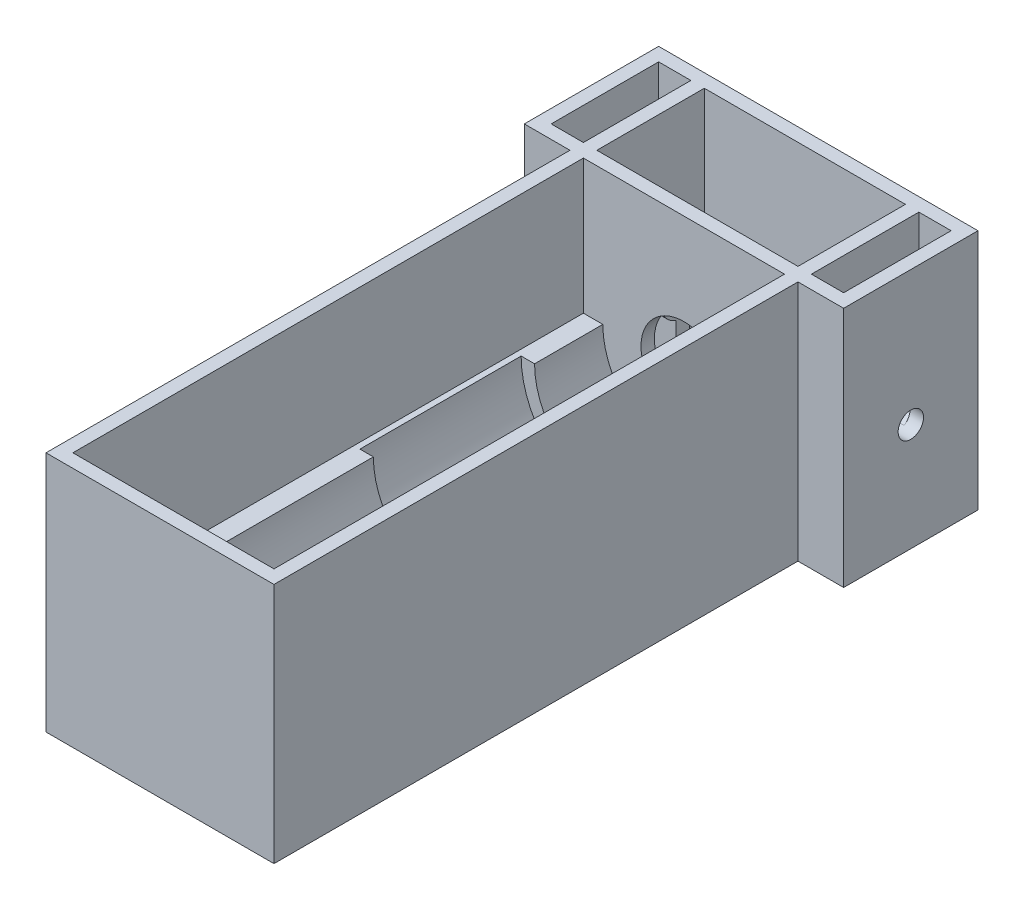
SolidWorks part; units mm, degrees
ref_plane "Front Plane" through (0, 0, 0) normal (0, 0, 1) x (1, 0, 0)
ref_plane "Top Plane" through (0, 0, 0) normal (0, 1, 0) x (1, 0, 0)
ref_plane "Right Plane" through (0, 0, 0) normal (1, 0, 0) x (0, 0, -1)
sketch "Sketch1" plane through (0, 0, 0) normal (0, 0, 1) x (1, 0, 0)
  line L1 (-26.9397, 0) -> (26.9397, 0)
  line L2 (-26.9397, 0) -> (-26.9397, 6.35)
  line L3 (-23.7647, 6.35) -> (23.7647, 6.35)
  line L4 (26.9397, 0) -> (26.9397, 6.35)
  line L6 (-26.9397, 6.35) -> (-26.9397, 57.15)
  line L7 (-26.9397, 57.15) -> (-23.7647, 57.15)
  line L8 (-23.7647, 6.35) -> (-23.7647, 57.15)
  line L10 (26.9397, 6.35) -> (26.9397, 57.15)
  line L11 (26.9397, 57.15) -> (23.7647, 57.15)
  line L12 (23.7647, 6.35) -> (23.7647, 57.15)
  dimension "D1" = 3.175
  dimension "D2" = 53.8795
  dimension "D3" = 6.35
  dimension "D4" = 50.8
extrude "Boss-Extrude1" add sketch "Sketch1" along normal mid plane 25.4
sketch "Sketch2" plane through (0, 0, -12.7) normal (0, 0, -1) x (-1, 0, 0)
  line L0 (26.9397, 0) -> (-26.9397, 0) construction
  line L1 (-26.9397, 57.15) -> (26.9397, 57.15)
  line L2 (-26.9397, 57.15) -> (-26.9397, 0)
  line L3 (-26.9397, 0) -> (26.9397, 0)
  line L4 (26.9397, 57.15) -> (26.9397, 0)
extrude "Boss-Extrude2" add sketch "Sketch2" along normal blind 3.175
sketch "Sketch6" plane through (0, 0, 0) normal (0, 0, 1) x (1, 0, 0)
  line L0 (-23.7647, 25.4) -> (-16.1447, 25.4)
  line L3 (-16.1447, 25.4) -> (-16.1447, 30.48)
  line L4 (-16.1447, 30.48) -> (-21.2247, 30.48)
  line L5 (-21.2247, 30.48) -> (-23.7647, 33.02)
  line L6 (0, 25.4) -> (0, 0) construction
  line L7 (-23.7647, 33.02) -> (-23.7647, 25.4)
  line L9 (-23.7647, 6.35) -> (-23.7647, 57.15) construction
  line L10 (23.7647, 33.02) -> (23.7647, 25.4)
  line L11 (21.2247, 30.48) -> (23.7647, 33.02)
  line L12 (16.1447, 30.48) -> (21.2247, 30.48)
  line L13 (16.1447, 25.4) -> (16.1447, 30.48)
  line L15 (23.7647, 25.4) -> (16.1447, 25.4)
  dimension "D1" = 5.08
  dimension "D2" = 5.08
  dimension "D3" = 7.62
  dimension "D4" = 7.62
  dimension "D5" = 25.4
revolve "Revolve2" add sketch "Sketch6" angle 360 about L0
sketch "Sketch3" plane through (0, 0, 0) normal (1, 0, 0) x (0, 0, -1)
  circle A0 centre (0, 25.4) radius 3
  circle A1 centre (0, 25.4) radius 5.08 construction
  dimension "D2" = 6
extrude "Cut-Extrude2" cut sketch "Sketch3" against normal through all both and the other way through all
sketch "Sketch5" plane through (0, 0, 0) normal (0, -1, 0) x (1, 0, 0)
  line L1 (26.9397, -15.875) -> (-26.9397, -15.875)
  line L2 (26.9397, -15.875) -> (26.9397, -41.275)
  line L3 (26.9397, -41.275) -> (-26.9397, -41.275)
  line L4 (-26.9397, -15.875) -> (-26.9397, -41.275)
  circle A0 centre (7.8897, -28.575) radius 3.4925
  circle A1 centre (-17.5103, -28.575) radius 3.4925
  point P9 (26.9397, -28.575)
  dimension "D2" = 6.985
  dimension "D1" = 25.4
  dimension "D3" = 19.05
  dimension "D4" = 2
extrude "Boss-Extrude3" add sketch "Sketch5" against normal blind 6.35
sketch "Sketch7" plane through (0, 0, 0) normal (0, 0, 1) x (1, 0, 0)
  line L0 (23.7647, 6.35) -> (-23.7647, 6.35) construction
  line L1 (-23.7647, 21.9594) -> (-16.1447, 21.9594)
  line L2 (-23.7647, 21.9594) -> (-23.7647, 6.35)
  line L3 (-23.7647, 6.35) -> (-16.1447, 6.35)
  line L4 (-16.1447, 21.9594) -> (-16.1447, 6.35)
  line L5 (-23.7647, 21.9594) -> (-16.1447, 6.35) construction
  line L6 (-23.7647, 6.35) -> (-16.1447, 21.9594) construction
  line L8 (0, 0) -> (0, 25.6446) construction
  line L9 (-26.9397, 0) -> (26.9397, 0) construction
  line L10 (23.7647, 6.35) -> (16.1447, 21.9594) construction
  line L11 (23.7647, 21.9594) -> (16.1447, 6.35) construction
  line L12 (16.1447, 21.9594) -> (16.1447, 6.35)
  line L13 (23.7647, 6.35) -> (16.1447, 6.35)
  line L14 (23.7647, 21.9594) -> (23.7647, 6.35)
  line L15 (23.7647, 21.9594) -> (16.1447, 21.9594)
  line L16 (-23.7647, 6.35) -> (-23.7647, 57.15) construction
  line L17 (-16.1447, 20.32) -> (-16.1447, 30.48) construction
  point P4 (-19.9547, 14.1547)
  point P18 (19.9547, 14.1547)
extrude "Boss-Extrude7" add sketch "Sketch7" along normal mid plane 3.175
sketch "Sketch8" plane through (0, 0, 12.7) normal (0, 0, 1) x (1, 0, 0)
  line L1 (-26.9397, 57.15) -> (26.9397, 57.15)
  line L2 (-26.9397, 57.15) -> (-26.9397, 0)
  line L3 (-26.9397, 0) -> (26.9397, 0)
  line L4 (26.9397, 57.15) -> (26.9397, 0)
  line L5 (-26.9397, 57.15) -> (26.9397, 0) construction
  line L6 (-26.9397, 0) -> (26.9397, 57.15) construction
  point P4 (0, 28.575)
extrude "Boss-Extrude8" add sketch "Sketch8" along normal blind 127
sketch "Sketch9" plane through (0, 0, 0) normal (1, 0, 0) x (0, 0, -1)
  line L0 (0, 25.4) -> (-139.7, 25.4) construction
  line L1 (-139.7, 0) -> (-139.7, 57.15) construction
  line L2 (-70.104, 47.752) -> (-70.104, 44.577)
  line L3 (-70.104, 47.752) -> (-32.004, 47.752)
  line L4 (-32.004, 47.752) -> (-32.004, 44.577)
  line L5 (-32.004, 44.577) -> (-20.1041, 44.577)
  line L6 (0, 35.56) -> (0, 25.4)
  line L7 (0, 25.4) -> (12.7, 25.4) construction
  line L8 (12.7, 6.35) -> (12.7, 57.15) construction
  line L9 (0, 25.4) -> (-70.104, 25.4)
  line L10 (-70.104, 44.577) -> (-136.525, 44.577)
  line L11 (-136.525, 44.577) -> (-136.525, 25.4)
  line L12 (-136.525, 25.4) -> (-70.104, 25.4)
  line L13 (-20.1041, 44.577) -> (-20.1041, 35.56)
  line L14 (-20.1041, 35.56) -> (0, 35.56)
  dimension "D1" = 38.1
  dimension "D2" = 10.16
  dimension "D3" = 22.352
  dimension "D4" = 3.175
  dimension "D5" = 3.175
revolve "Cut-Revolve1" cut sketch "Sketch9" angle 360 about L9
ref_axis "Axis2" through (0, 25.4, 70.104) along (0, 0, -1)
ref_axis "Axis3" through (-26.9397, 25.4, 0) along (1, 0, 0)
ref_plane "Plane2" through (0, 25.4, 0) normal (0, -1, 0) x (-1, 0, 0)
sketch "Sketch13" plane through (0, 0, 0) normal (0, -1, 0) x (-1, 0, 0)
  line L0 (26.9397, -139.7) -> (26.9397, 41.275) construction
  line L1 (26.9397, -15.4709) -> (26.9421, -15.4709)
  line L2 (26.9397, -15.4709) -> (26.9397, -139.7)
  line L3 (26.9397, -139.7) -> (26.9421, -139.7)
  line L4 (26.9421, -15.4709) -> (26.9421, -139.7)
  line L5 (26.9397, -15.4709) -> (26.9421, -139.7) construction
  line L6 (26.9397, -139.7) -> (26.9421, -15.4709) construction
  line L7 (26.9397, -139.7) -> (-26.9397, -139.7) construction
  line L9 (-26.9397, -139.7) -> (-26.9374, -139.7)
  line L10 (-26.9397, -139.7) -> (-26.9397, -15.4709)
  line L11 (-26.9397, -15.4709) -> (-26.9374, -15.4709)
  line L12 (-26.9374, -139.7) -> (-26.9374, -15.4709)
  line L13 (-26.9397, -139.7) -> (-26.9374, -15.4709) construction
  line L14 (-26.9397, -15.4709) -> (-26.9374, -139.7) construction
  point P4 (26.9409, -77.5855)
  point P13 (-26.9386, -77.5855)
extrude "Cut-Extrude7" cut sketch "Sketch13" against normal through all both and the other way through all
sketch "Sketch14" plane through (0, 57.15, 0) normal (0, 1, 0) x (1, 0, 0)
  line L1 (23.7624, -136.525) -> (-23.7647, -136.525)
  line L2 (23.7624, -136.525) -> (23.7624, -15.875)
  line L3 (23.7624, -15.875) -> (-23.7647, -15.875)
  line L4 (-23.7647, -136.525) -> (-23.7647, -15.875)
  line L5 (23.7624, -136.525) -> (-23.7647, -15.875) construction
  line L6 (23.7624, -15.875) -> (-23.7647, -136.525) construction
  line L7 (26.9374, -139.7) -> (-26.9397, -139.7) construction
  line L8 (26.9374, -139.7) -> (26.9374, -15.4709) construction
  line L10 (23.7647, -12.7) -> (-23.7647, -12.7) construction
  line L11 (-26.9397, -139.7) -> (-26.9397, 15.875) construction
  point P4 (-0.0012, -76.2)
  dimension "D1" = 3.175
  dimension "D2" = 3.175
  dimension "D3" = 3.175
  dimension "D4" = 3.175
extrude "Cut-Extrude8" cut sketch "Sketch14" against normal up to surface (31.75 mm away) up to plane "Plane2"
sketch "Sketch15" plane through (0, 0, 20.1041) normal (0, 0, 1) x (1, 0, 0)
  line L2 (-10.16, 25.4) -> (-19.177, 25.4)
  line L3 (19.177, 25.4) -> (10.16, 25.4)
  line L4 (-10.16, 25.4) -> (-19.177, 25.4)
  line L5 (19.177, 25.4) -> (10.16, 25.4)
  arc A2 (-19.177, 25.4) -> (19.177, 25.4) centre (0, 25.4) ccw
  arc A3 (-10.16, 25.4) -> (10.16, 25.4) centre (0, 25.4) ccw
  arc A4 (-19.177, 25.4) -> (19.177, 25.4) centre (0, 25.4) ccw
  arc A5 (-10.16, 25.4) -> (10.16, 25.4) centre (0, 25.4) ccw
  dimension "D1" = 0
extrude "Cut-Extrude9" cut sketch "Sketch15" against normal up to surface (4.2291 mm away) up to face at (-0.0008, 37.6767, 15.875)
sketch "Sketch16" plane through (0, 6.35, 0) normal (0, 1, 0) x (1, 0, 0)
  line L1 (26.9397, 41.275) -> (-26.9397, 41.275)
  line L2 (26.9397, 41.275) -> (26.9397, 15.875)
  line L3 (26.9397, 15.875) -> (-26.9397, 15.875)
  line L4 (-26.9397, 41.275) -> (-26.9397, 15.875)
  line L5 (26.9397, 41.275) -> (-26.9397, 15.875) construction
  line L6 (26.9397, 15.875) -> (-26.9397, 41.275) construction
  point P4 (0, 28.575)
extrude "Cut-Extrude10" cut sketch "Sketch16" against normal through all
sketch "Sketch18" plane through (0, 0, 0) normal (0, 1, 0) x (1, 0, 0)
  line L0 (-26.9397, 15.875) -> (26.9397, 15.875) construction
  line L1 (-23.7647, 15.875) -> (-37.7347, 15.875)
  line L2 (-23.7647, 15.875) -> (-23.7647, -15.875)
  line L3 (-23.7647, -15.875) -> (-37.7347, -15.875)
  line L4 (-37.7347, 15.875) -> (-37.7347, -15.875)
  line L5 (-23.7647, 15.875) -> (-37.7347, -15.875) construction
  line L6 (-23.7647, -15.875) -> (-37.7347, 15.875) construction
  line L7 (-23.7647, -12.7) -> (-23.7647, 12.7) construction
  line L8 (-19.177, -15.875) -> (-23.7647, -15.875) construction
  line L9 (-26.9397, -139.7) -> (-26.9397, 15.875) construction
  line L10 (-34.5597, 12.7) -> (-26.9397, 12.7)
  line L11 (-34.5597, 12.7) -> (-34.5597, -12.7)
  line L12 (-34.5597, -12.7) -> (-26.9397, -12.7)
  line L13 (-26.9397, 12.7) -> (-26.9397, -12.7)
  line L14 (-34.5597, 12.7) -> (-26.9397, -12.7) construction
  line L15 (-34.5597, -12.7) -> (-26.9397, 12.7) construction
  point P4 (-30.7497, 0)
  point P15 (-30.7497, 0)
  dimension "D1" = 7.62
  dimension "D2" = 3.175
  dimension "D3" = 3.175
extrude "Boss-Extrude10" add sketch "Sketch18" along normal up to surface (57.15 mm away) up to face at (-0.0012, 57.15, 76.2)
sketch "Sketch19" plane through (0, 0, 0) normal (1, 0, 0) x (0, 0, -1)
  line L0 (1.5875, 22.8544) -> (12.7, 29.7846)
  line L1 (12.7, 6.35) -> (12.7, 57.15) construction
  line L2 (-1.5875, 22.8544) -> (-12.7, 29.7846)
  line L3 (-12.7, 15.24) -> (-12.7, 35.56) construction
  line L4 (-12.7, 29.7846) -> (-12.7, 0)
  line L5 (-12.7, 0) -> (12.7, 0)
  line L6 (12.7, 0) -> (12.7, 29.7846)
  arc A0 (-1.5875, 22.8544) -> (1.5875, 22.8544) centre (0, 25.4) ccw
  circle A1 centre (0, 25.4) radius 3 construction
  dimension "D1" = 3.175
extrude "Boss-Extrude11" add sketch "Sketch19" against normal up to next from surface starting at face at (-26.9397, 28.575, 77.7875)
mirror "Mirror4" about plane through (0, 0, 0) normal (1, 0, 0) of "Boss-Extrude10"
extrude "Boss-Extrude12" add sketch "Sketch19<2>" along normal up to next from surface starting at face at (26.9397, 28.575, 0)
sketch "Sketch19<2>" plane through (0, 0, 0) normal (1, 0, 0) x (0, 0, -1) same geometry as "Sketch19"
sketch "Sketch20" plane through (-23.7647, 0, 0) normal (1, 0, 0) x (0, 0, -1)
  circle A0 centre (0, 25.4) radius 3 construction
  circle A1 centre (0, 25.4) radius 3
extrude "Cut-Extrude11" cut sketch "Sketch20" against normal through all both and the other way through all
